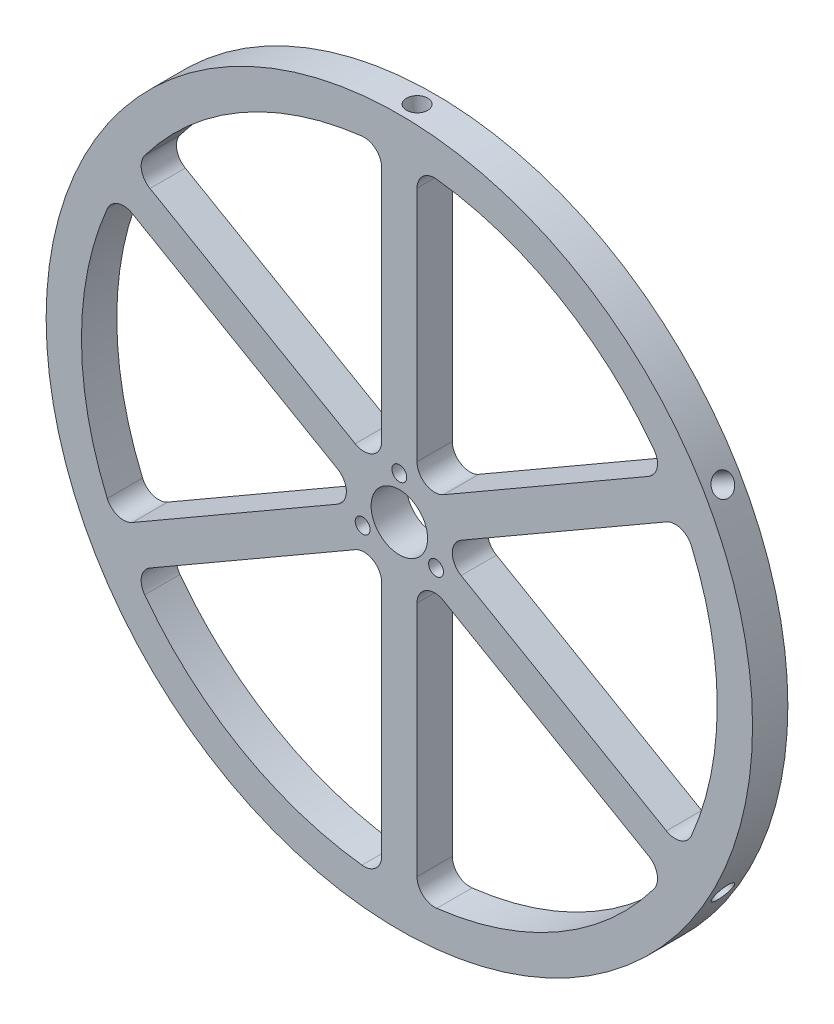
SolidWorks part; units mm, degrees
ref_plane "Front" through (0, 0, 0) normal (0, 0, 1) x (1, 0, 0)
ref_plane "Top" through (0, 0, 0) normal (0, 1, 0) x (1, 0, 0)
ref_plane "Right" through (0, 0, 0) normal (1, 0, 0) x (0, 0, -1)
sketch "Esquisse1" plane through (0, 0, 0) normal (0, 0, 1) x (1, 0, 0)
  circle A0 centre (0, 0) radius 100
  dimension "D1" = 200
extrude "Boss.-Extru.1" add sketch "Esquisse1" along normal blind 10
sketch "Esquisse2" plane through (0, 0, 10) normal (0, 0, 1) x (1, 0, 0)
  line L0 (0, 0) -> (10, 0) construction
  line L1 (10, 0) -> (80.3219, 40.6004)
  line L2 (80, 0) -> (10, 0) construction
  line L3 (10, 0) -> (80.3219, -40.6004)
  line L4 (5, -8.6603) -> (75.3219, -49.2606)
  line L5 (5, -8.6603) -> (5, -89.861)
  line L6 (0, 0) -> (5, -8.6603) construction
  line L7 (40, -69.282) -> (5, -8.6603) construction
  line L8 (-5, -8.6603) -> (-5, -89.861)
  line L9 (-5, -8.6603) -> (-75.3219, -49.2606)
  line L10 (0, 0) -> (-5, -8.6603) construction
  line L11 (-40, -69.282) -> (-5, -8.6603) construction
  line L12 (-10, 0) -> (-80.3219, -40.6004)
  line L13 (-10, 0) -> (-80.3219, 40.6004)
  line L14 (0, 0) -> (-10, 0) construction
  line L15 (-80, 0) -> (-10, 0) construction
  line L16 (-5, 8.6603) -> (-75.3219, 49.2606)
  line L17 (-5, 8.6603) -> (-5, 89.861)
  line L18 (0, 0) -> (-5, 8.6603) construction
  line L19 (-40, 69.282) -> (-5, 8.6603) construction
  line L20 (5, 8.6603) -> (5, 89.861)
  line L21 (5, 8.6603) -> (75.3219, 49.2606)
  line L22 (0, 0) -> (5, 8.6603) construction
  line L23 (40, 69.282) -> (5, 8.6603) construction
  arc A0 (80.3219, 40.6004) -> (80.3219, -40.6004) centre (0, 0) cw
  circle A1 centre (0, 0) radius 100 construction
  arc A2 (75.3219, -49.2606) -> (5, -89.861) centre (0, 0) cw
  arc A3 (-5, -89.861) -> (-75.3219, -49.2606) centre (0, 0) cw
  arc A4 (-80.3219, -40.6004) -> (-80.3219, 40.6004) centre (0, 0) cw
  arc A5 (-75.3219, 49.2606) -> (-5, 89.861) centre (0, 0) cw
  arc A6 (5, 89.861) -> (75.3219, 49.2606) centre (0, 0) cw
  point P8 (74.0931, 30.1697)
  point P9 (63.6286, 48.4912)
  point P30 (0, 0)
  dimension "D1" = 10
  dimension "D3" = 10
  dimension "D2" = 6
extrude "Enlèv. mat.-Extru.1" cut sketch "Esquisse2" against normal through all both and the other way through all
fillet "Congé1" radius 5 18 edges at (-5, 8.6603, 5) (-10, 0, 5) (-5, -8.6603, 5) (5, -8.6603, 5) (10, 0, 5) (80.3219, 40.6004, 5) (80.3219, -40.6004, 5) (75.3219, -49.2606, 5) (5, -89.861, 5) (-5, -89.861, 5) (-75.3219, -49.2606, 5) (-80.3219, -40.6004, 5) (-80.3219, 40.6004, 5) (-75.3219, 49.2606, 5) (-5, 89.861, 5) (5, 89.861, 5) (75.3219, 49.2606, 5) (5, 8.6603, 5)
sketch "Esquisse3" plane through (0, 0, 10) normal (0, 0, 1) x (1, 0, 0)
  circle A0 centre (0, 0) radius 8
  dimension "D1" = 16
extrude "Enlèv. mat.-Extru.2" cut sketch "Esquisse3" against normal through all both and the other way through all
sketch "Esquisse4" plane through (0, 0, 10) normal (0, 0, 1) x (1, 0, 0)
  line L0 (0, 0) -> (0, 12) construction
  line L1 (0, 0) -> (-10.3923, -6) construction
  line L2 (0, 0) -> (10.3923, -6) construction
  circle A0 centre (0, 12) radius 2.1
  circle A2 centre (10.3923, -6) radius 2.1
  circle A3 centre (-10.3923, -6) radius 2.1
  point P9 (-10.7214, -6)
  dimension "D1" = 4.2
  dimension "D2" = 12
  dimension "D3" = 120
  dimension "D4" = 120
extrude "Enlèv. mat.-Extru.3" cut sketch "Esquisse4" against normal through all both and the other way through all
sketch "Esquisse5" plane through (0, 0, 0) normal (0, 1, 0) x (0, 0, -1)
  line L0 (0, 0) -> (-10, 0) construction
  line L1 (0, -100) -> (0, 100) construction
  line L2 (-10, 100) -> (-10, -100) construction
  circle A0 centre (-5, 0) radius 3
  dimension "D1" = 6
extrude "Enlèv. mat.-Extru.4" cut sketch "Esquisse5" against normal blind 10 from offset 100
pattern_circular "Répétition circulaire1" count 6 over 360 about axis through (0, 0, 10) along (0, 0, 1) of "Enlèv. mat.-Extru.4"
